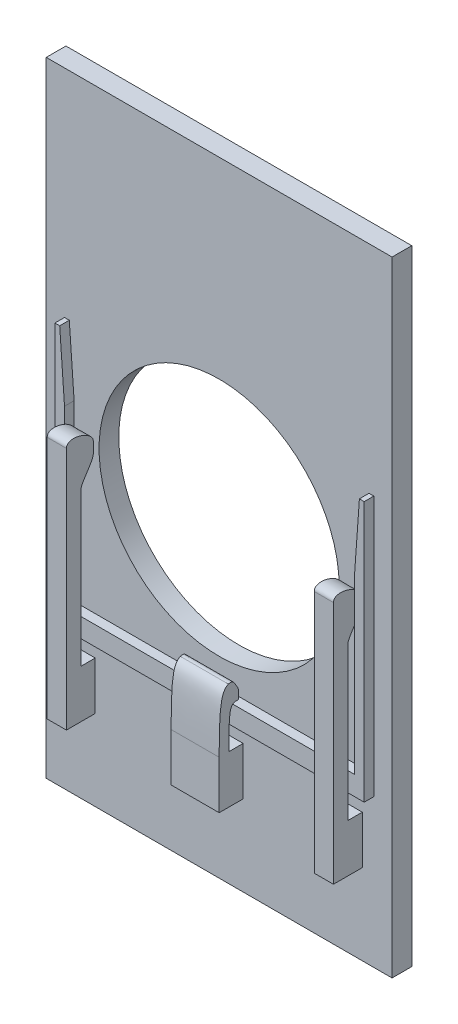
SolidWorks part; units mm, degrees
ref_plane "Front Plane" through (0, 0, 0) normal (0, 0, 1) x (1, 0, 0)
ref_plane "Top Plane" through (0, 0, 0) normal (0, 1, 0) x (1, 0, 0)
ref_plane "Right Plane" through (0, 0, 0) normal (1, 0, 0) x (0, 0, -1)
sketch "main_features_sketch" plane through (0, 0, 0) normal (0, 0, 1) x (1, 0, 0)
  line L0 (15.1, 0) -> (16.1, 0) construction
  line L1 (18, 32.5) -> (-18, 32.5)
  line L2 (18, 32.5) -> (18, -32.5)
  line L3 (18, -32.5) -> (-18, -32.5)
  line L4 (-18, 32.5) -> (-18, -32.5)
  line L5 (0, -32.5) -> (0, 32.5) construction
  line L6 (18, 0) -> (-18, 0) construction
  line L13 (-15.1, 0) -> (-16.1, 0) construction
  line L14 (-16.1, 0) -> (-16.1, 10)
  line L15 (-15.1, 0) -> (-15.1, 3)
  line L16 (-15.1, 3) -> (-15.6, 10)
  line L17 (-15.6, 10) -> (-16.1, 10)
  line L18 (15.1, 0) -> (15.1, 3)
  line L19 (15.1, 3) -> (15.6, 10)
  line L20 (15.6, 10) -> (16.1, 10)
  line L21 (16.1, 10) -> (16.1, 0)
  line L22 (15.1, 0) -> (15.1, -15.1)
  line L23 (15.1, -15.1) -> (-15.1, -15.1)
  line L24 (-15.1, -15.1) -> (-15.1, 0)
  line L25 (16.1, 0) -> (16.1, -17.1)
  line L26 (16.1, -17.1) -> (-16.1, -17.1)
  line L27 (-16.1, -17.1) -> (-16.1, 0)
  line L29 (-15.1, -15.1) -> (-16.1, -15.1) construction
  line L30 (15.1, -15.1) -> (16.1, -15.1) construction
  circle A0 centre (0, 0) radius 12.5
  circle A1 centre (0, 0) radius 15.1 construction
  point P0 (0, 0)
  point P25 (0, 0)
  point P29 (0, 0)
  dimension "D1" = 25
  dimension "D4" = 30.2
  dimension "D2" = 36
  dimension "D3" = 65
  dimension "D8" = 1
  dimension "D9" = 3
  dimension "D10" = 10
  dimension "D11" = 0.5
  dimension "D5" = 2
extrude "base_filter" add sketch "main_features_sketch" along normal blind 2.05 contours L1 L4 L3 L2 A0 | L14 L21 L20 L19 L18 L15 L16 L17 region at (17.257, 0, 0) region at (-15.6791, 5, 0)
extrude "lens_surround" add sketch "main_features_sketch<4>" along normal blind 3.05 contours L14 L21 L20 L19 L18 L15 L16 L17 region at (-15.6791, 5, 0)
sketch "main_features_sketch<4>" plane through (0, 0, 0) normal (0, 0, 1) x (1, 0, 0) same geometry as "main_features_sketch"
sketch "arm_sketch" plane through (0, 0, 0) normal (-1, 0, 0) x (0, -1, 0)
  line L2 (15.398, 4.55) -> (22.802, 4.55) construction
  line L5 (15.3214, 3.55) -> (22.8786, 3.55) construction
  line L6 (14.9, 2.5494) -> (13.9, 2.5494)
  line L7 (13.9, 2.5494) -> (12.9, 3.1347)
  line L9 (17.1, 3.05) -> (17.1, 2.05) construction
  line L18 (19.1, 3.55) -> (19.1, 4.55) construction
  line L19 (19.1, 3.55) -> (24.1, 3.55) construction
  line L20 (19.1, 2.05) -> (19.1, 3.55)
  line L21 (24.1, 2.05) -> (19.1, 2.05)
  line L22 (24.1, 3.55) -> (24.1, 2.05)
  line L24 (24.1, 4.55) -> (19.1, 4.55)
  line L25 (24.1, 3.55) -> (24.1, 4.55)
  line L26 (-32.5, 2.05) -> (32.5, 2.05) construction
  spline S2 degree 3 poles (19.1, 3.55) (14.8829, 3.55) (14.9, 3.3863) (14.9, 2.5494) knots 0 0 0 0 1 1 1 1
  spline S3 degree 3 poles (19.1, 4.55) (14.0971, 4.55) (12.9, 4.3386) (12.9, 3.1347) knots 0 0 0 0 1 1 1 1
  point P2 (13.9, 2.5494)
  point P7 (14.0751, 2.9081)
  point P8 (13.9515, 3.1347)
  dimension "D2" = 2
  dimension "D3" = 1
  dimension "D9" = 5
  dimension "D10" = 2
  dimension "D11" = 1
  dimension "D12" = 1.5
  dimension "D14" = 0.2
extrude "arm" add sketch "arm_sketch" against normal mid plane 5 contours S3 L24 L25 L22 L21 L20 S2 region at (0, -19.4565, 3.4723)
fillet "Fillet1" radius 0.5 2 edges at (0, -13.9, 2.5494) (0, -12.9, 3.1347)
sketch "long_arm_sketch" plane through (-15.1, 0, 0) normal (1, 0, 0) x (0, 0, -1)
  line L0 (-2.05, -24.1) -> (-5.05, -24.1)
  line L1 (-2.05, -24.1) -> (-2.05, -19.1) construction
  line L2 (-5.05, -24.1) -> (-5.05, 1.2977)
  line L3 (-2.05, -24.1) -> (-2.05, -19.1)
  line L4 (-2.05, -19.1) -> (-3.55, -19.1)
  line L5 (-3.55, -19.1) -> (-3.55, -3.2112)
  line L6 (-2.25, -0.5376) -> (-2.25, 0.5376)
  line L7 (-3.55, -4.6588) -> (-3.55, -6.2054) construction
  line L8 (-2.25, -3.6307) -> (-2.25, -4.8351) construction
  line L9 (-5.05, -1.8402) -> (-5.05, -2.4144) construction
  line L10 (-2.25, -3.6782) -> (-2.25, -2.56) construction
  line L11 (-3.05, -17.1) -> (-2.05, -17.1) construction
  line L12 (-2.05, 3) -> (-2.05, -15.1) construction
  line L13 (0, 0) -> (-2.25, 0) construction
  spline S0 degree 3 poles (-5.05, 1.2977) (-5.05, 2.3943) (-2.25, 1.5664) (-2.25, 0.5376) knots 0 0 0 0 1 1 1 1
  spline S1 degree 3 poles (-3.55, -3.2112) (-3.55, -2.5668) (-2.25, -1.2904) (-2.25, -0.5376) knots 0 0 0 0 1 1 1 1
  point P14 (-4.55, 1.2977)
  point P17 (-3.55, -2.3447)
  dimension "D1" = 1.5
  dimension "D2" = 1.5
  dimension "D3" = 5
  dimension "D4" = 2
  dimension "D5" = 0.2
extrude "long_arm" add sketch "long_arm_sketch" along normal blind 2 from offset 0.2
mirror "Mirror1" about plane through (0, 0, 0) normal (1, 0, 0) of "long_arm"
equation "\"hole_diameter\" = 25mm"
equation "\"D1@main_features_sketch\" = \"hole_diameter\""
equation "\"filter_width\" = 36mm"
equation "\"D2@main_features_sketch\" = \"filter_width\""
equation "\"filter_height\" = 65mm"
equation "\"D3@main_features_sketch\" = \"filter_height\""
equation "\"lens_diameter\" = 30mm"
equation "\"D4@main_features_sketch\"=\"lens_diameter\"+.2"
equation "\"lens_thickness\"= 1mm"
equation "\"filter_thickness\"= 2.05mm"
equation "\"D1@base_filter\"=\"filter_thickness\""
equation "\"D1@lens_surround\"=\"lens_thickness\"+\"filter_thickness\""
